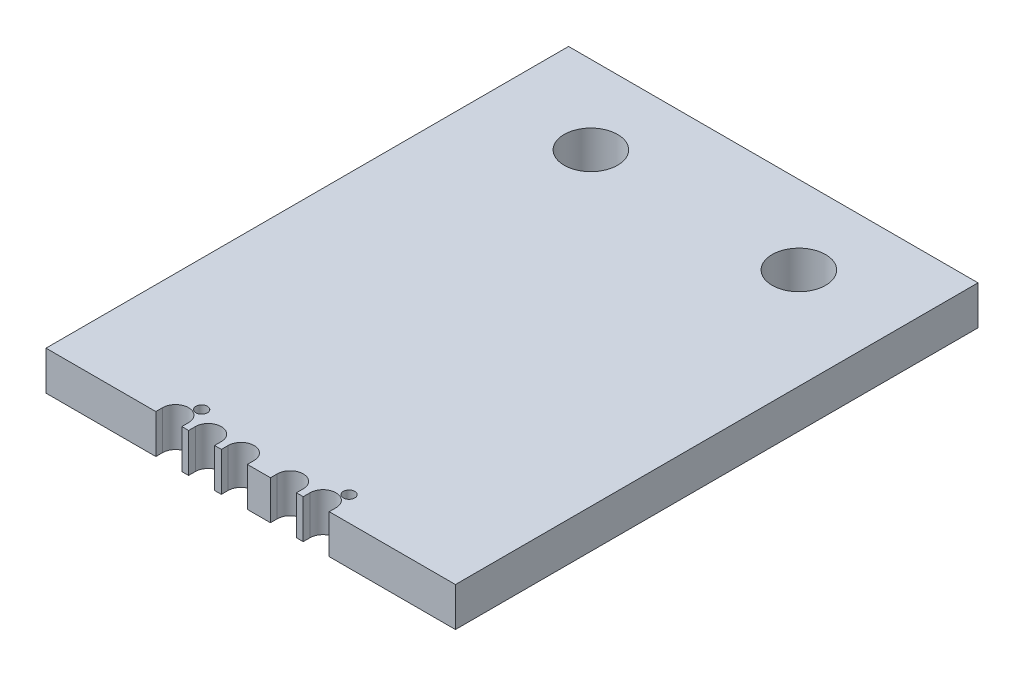
SolidWorks part; units mm, degrees
ref_plane "Front Plane" through (0, 0, 0) normal (0, 0, 1) x (1, 0, 0)
ref_plane "Top Plane" through (0, 0, 0) normal (0, 1, 0) x (1, 0, 0)
ref_plane "Right Plane" through (0, 0, 0) normal (1, 0, 0) x (0, 0, -1)
sketch "Sketch1" plane through (0, 0, 0) normal (0, 1, 0) x (1, 0, 0)
  line L0 (16, 1.1851) -> (30, 1.1851) construction
  line L1 (16, 1.1851) -> (66, 1.1851) construction
  line L2 (16, 1.1851) -> (16, 65)
  line L3 (16, 65) -> (66, 65)
  line L4 (66, 1.1851) -> (66, 65)
  line L5 (66, 1.1851) -> (52, 1.1851) construction
  line L6 (30, 1.1851) -> (30, 3.5973) construction
  line L7 (30, 3.5973) -> (31, 3.5973) construction
  line L8 (52, 3.5973) -> (52, 1.1851) construction
  line L9 (32, 4.1973) -> (32, 3.5973) construction
  line L10 (31, 3.5973) -> (33, 3.5973) construction
  line L11 (53.7, 55.4261) -> (28.3, 55.4261) construction
  line L12 (33, 3.5973) -> (35, 3.5973) construction
  line L13 (35, 3.5973) -> (37, 3.5973) construction
  line L14 (37, 3.5973) -> (39, 3.5973) construction
  line L15 (39, 3.5973) -> (41, 3.5973) construction
  line L16 (41, 3.5973) -> (43, 3.5973) construction
  line L17 (43, 3.5973) -> (45, 3.5973) construction
  line L18 (45, 3.5973) -> (47, 3.5973) construction
  line L19 (47, 3.5973) -> (49, 3.5973) construction
  line L20 (49, 3.5973) -> (51, 3.5973) construction
  line L21 (51, 3.5973) -> (52, 3.5973) construction
  line L22 (29.4125, 1.1851) -> (29.4125, 2.0098) construction
  line L23 (53.7, 55.4261) -> (66, 55.4261) construction
  line L24 (29.4125, 2.0098) -> (32.5875, 2.0098) construction
  line L25 (32.5875, 2.0098) -> (32.5875, 1.1851) construction
  line L26 (33.4125, 1.1851) -> (33.4125, 2.0098) construction
  line L27 (28.3, 55.4261) -> (16, 55.4261) construction
  line L28 (33.4125, 2.0098) -> (36.5875, 2.0098) construction
  line L29 (36.5875, 2.0098) -> (36.5875, 1.1851) construction
  line L30 (37.4125, 1.1851) -> (37.4125, 2.0098) construction
  line L31 (37.4125, 2.0098) -> (40.5875, 2.0098) construction
  line L32 (40.5875, 2.0098) -> (40.5875, 1.1851) construction
  line L33 (43.4125, 1.1851) -> (43.4125, 2.0098) construction
  line L34 (43.4125, 2.0098) -> (46.5875, 2.0098) construction
  line L35 (46.5875, 2.0098) -> (46.5875, 1.1851) construction
  line L36 (47.4125, 1.1851) -> (47.4125, 2.0098) construction
  line L37 (47.4125, 2.0098) -> (50.5875, 2.0098) construction
  line L38 (50.5875, 2.0098) -> (50.5875, 1.1851) construction
  line L39 (16, 1.1851) -> (29.4125, 1.1851)
  line L40 (29.4125, 1.1851) -> (29.4125, 2.0098)
  line L41 (50.5875, 2.0098) -> (50.5875, 1.1851)
  line L42 (50.5875, 1.1851) -> (66, 1.1851)
  line L43 (46.5875, 2.0098) -> (46.5875, 1.1851)
  line L44 (46.5875, 1.1851) -> (47.4125, 1.1851)
  line L45 (47.4125, 1.1851) -> (47.4125, 2.0098)
  line L46 (43.4125, 2.0098) -> (43.4125, 1.1851)
  line L47 (43.4125, 1.1851) -> (40.5875, 1.1851)
  line L48 (40.5875, 1.1851) -> (40.5875, 2.0098)
  line L49 (37.4125, 2.0098) -> (37.4125, 1.1851)
  line L50 (37.4125, 1.1851) -> (36.5875, 1.1851)
  line L51 (36.5875, 1.1851) -> (36.5875, 2.0098)
  line L52 (33.4125, 2.0098) -> (33.4125, 1.1851)
  line L53 (33.4125, 1.1851) -> (32.5875, 1.1851)
  line L54 (32.5875, 1.1851) -> (32.5875, 2.0098)
  arc A0 (29.4125, 2.0098) -> (32.5875, 2.0098) centre (31, 2.0098) cw
  arc A1 (33.4125, 2.0098) -> (36.5875, 2.0098) centre (35, 2.0098) cw
  arc A2 (37.4125, 2.0098) -> (40.5875, 2.0098) centre (39, 2.0098) cw
  circle A3 centre (32, 4.1973) radius 0.7
  circle A4 centre (53.7, 55.4261) radius 3.2639
  circle A5 centre (28.3, 55.4261) radius 3.2639
  circle A6 centre (50, 4.1973) radius 0.7
  arc A7 (43.4125, 2.0098) -> (46.5875, 2.0098) centre (45, 2.0098) cw
  arc A8 (47.4125, 2.0098) -> (50.5875, 2.0098) centre (49, 2.0098) cw
extrude "Boss-Extrude1" add sketch "Sketch1" against normal blind 4.7625
ref_axis "Axis1" through (32, -4.7625, -4.1973) along (0, 1, 0)
ref_axis "Axis2" through (50, -4.7625, -4.1973) along (0, 1, 0)
